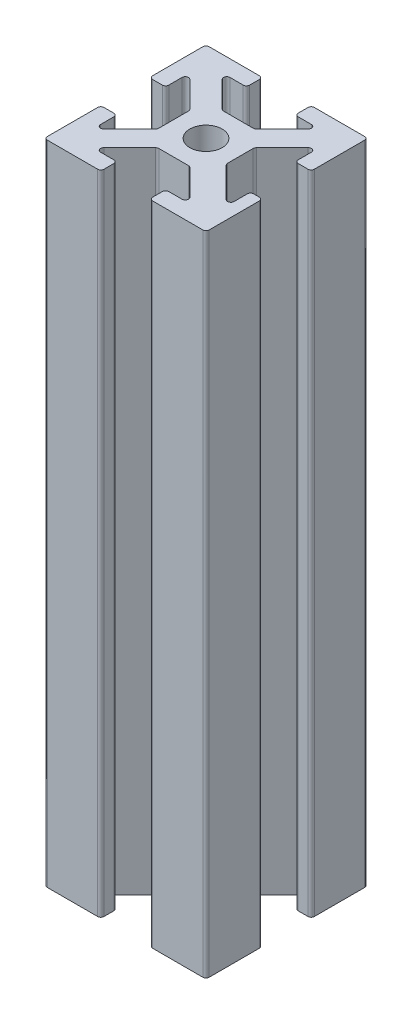
SolidWorks part; units mm, degrees
ref_plane "Plan de face" through (0, 0, 0) normal (0, 0, 1) x (1, 0, 0)
ref_plane "Plan de dessus" through (0, 0, 0) normal (0, 1, 0) x (1, 0, 0)
ref_plane "Plan de droite" through (0, 0, 0) normal (1, 0, 0) x (0, 0, -1)
sketch "Esquisse1" plane through (0, 0, 0) normal (0, 1, 0) x (1, 0, 0)
  line L0 (0, 0) -> (20, 0) construction
  line L1 (20, 0) -> (20, 20) construction
  line L2 (20, 20) -> (0, 20) construction
  line L3 (0, 20) -> (0, 0) construction
  line L4 (0, 0) -> (20, 20) construction
  line L5 (20, 20) -> (0, 20) construction
  line L6 (0, 20) -> (20, 0) construction
  line L7 (0, 0) -> (0, 7)
  line L8 (0, 20) -> (0, 13)
  line L9 (0, 20) -> (7, 20)
  line L10 (20, 20) -> (20, 13)
  line L11 (20, 20) -> (13, 20)
  line L12 (20, 0) -> (20, 7)
  line L13 (20, 0) -> (13, 0)
  line L14 (0, 0) -> (7, 0)
  line L15 (0, 7) -> (2, 7)
  line L16 (0, 13) -> (2, 13)
  line L17 (2, 13) -> (2, 16)
  line L18 (7, 0) -> (7, 2)
  line L19 (13, 0) -> (13, 2)
  line L20 (13, 2) -> (16, 2)
  line L21 (20, 7) -> (18.5, 7)
  line L22 (18.5, 7) -> (18.5, 4)
  line L23 (20, 13) -> (18, 13)
  line L24 (18, 13) -> (18, 16)
  line L25 (13, 20) -> (13, 18)
  line L26 (13, 18) -> (16, 18)
  line L27 (7, 20) -> (7, 18)
  line L28 (7, 18) -> (4, 18)
  line L29 (10, 10) -> (10, 14) construction
  line L30 (10, 14) -> (14, 14) construction
  line L31 (14, 14) -> (14, 6) construction
  line L32 (14, 6) -> (6, 6) construction
  line L33 (6, 6) -> (6, 14) construction
  line L34 (6, 14) -> (10, 14) construction
  line L42 (7, 2) -> (4, 2)
  line L44 (2, 7) -> (2, 4)
  line L49 (2, 4) -> (6, 8)
  line L50 (4, 2) -> (8, 6)
  line L51 (8, 6) -> (12, 6)
  line L52 (12, 6) -> (16, 2)
  line L53 (2, 16) -> (6, 12)
  line L54 (6, 12) -> (6, 8)
  line L55 (18.5, 4) -> (14, 8.5)
  line L56 (14, 8.5) -> (14, 12)
  line L57 (14, 12) -> (18, 16)
  line L58 (16, 18) -> (12, 14)
  line L59 (12, 14) -> (8, 14)
  line L60 (8, 14) -> (4, 18)
  circle A0 centre (10, 10) radius 2
extrude "Boss.-Extru.1" add sketch "Esquisse1" along normal blind 80
fillet "Congé1" radius 0.4 36 edges at (4, 40, -18) (2, 40, -16) (6, 40, -12) (6, 40, -8) (2, 40, -4) (2, 40, -7) (0, 40, -7) (0, 40, 0) (7, 40, 0) (7, 40, -2) (4, 40, -2) (8, 40, -6) (12, 40, -6) (16, 40, -2) (13, 40, -2) (13, 40, 0) (20, 40, 0) (20, 40, -7) (18.5, 40, -7) (18.5, 40, -4) (14, 40, -8.5) (14, 40, -12) (18, 40, -16) (18, 40, -13) (20, 40, -13) (20, 40, -20) (13, 40, -20) (13, 40, -18) (16, 40, -18) (12, 40, -14) (8, 40, -14) (7, 40, -18) (7, 40, -20) (0, 40, -20) (0, 40, -13) (2, 40, -13) first distance on face at (6, 40, -16) first distance on face at (2, 40, -14.5) first distance on face at (4, 40, -14) first distance on face at (6, 40, -10) first distance on face at (4, 40, -6) first distance on face at (2, 40, -5.5) first distance on face at (1, 40, -7) first distance on face at (0, 40, -3.5) first distance on face at (3.5, 40, 0) first distance on face at (7, 40, -1) first distance on face at (5.5, 40, -2) first distance on face at (6, 40, -4) first distance on face at (10, 40, -6) first distance on face at (14, 40, -4) first distance on face at (14.5, 40, -2) first distance on face at (13, 40, -1) first distance on face at (16.5, 40, 0) first distance on face at (20, 40, -3.5) first distance on face at (19.25, 40, -7) first distance on face at (18.5, 40, -5.5) first distance on face at (16.25, 40, -6.25) first distance on face at (14, 40, -10.25) first distance on face at (16, 40, -14) first distance on face at (18, 40, -14.5) first distance on face at (19, 40, -13) first distance on face at (20, 40, -16.5) first distance on face at (16.5, 40, -20) first distance on face at (13, 40, -19) first distance on face at (14.5, 40, -18) first distance on face at (14, 40, -16) first distance on face at (10, 40, -14) first distance on face at (5.5, 40, -18) first distance on face at (7, 40, -19) first distance on face at (3.5, 40, -20) first distance on face at (0, 40, -16.5) first distance on face at (1, 40, -13)
